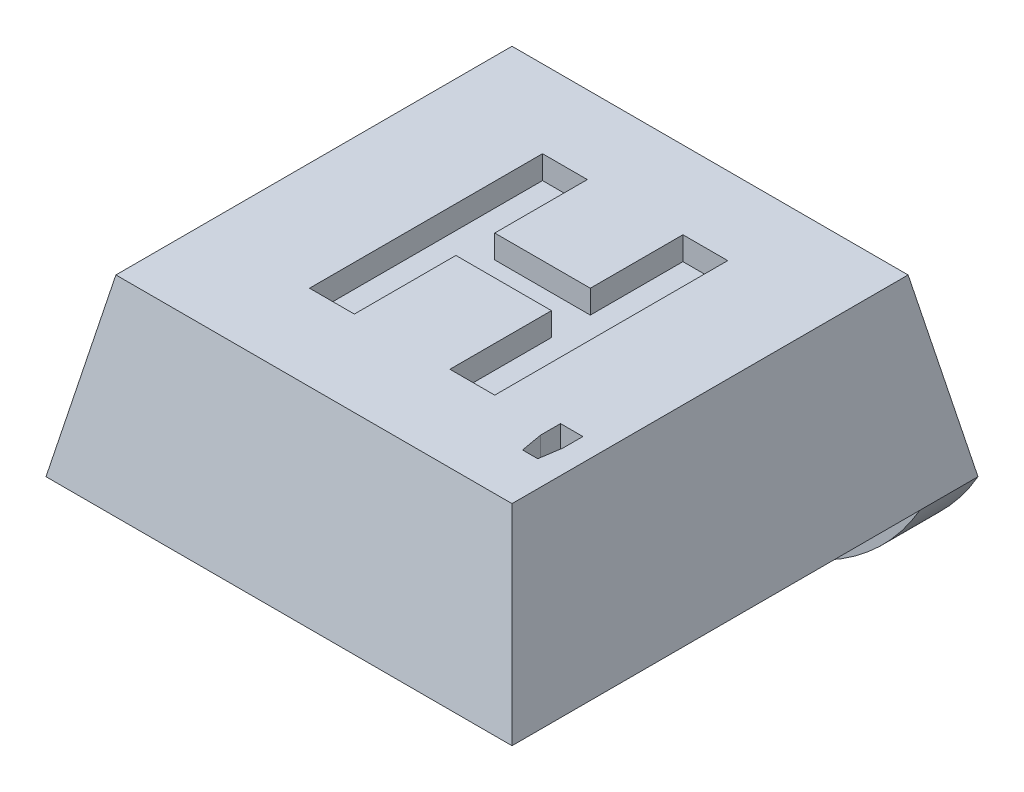
SolidWorks part; units mm, degrees
ref_plane "Front Plane" through (0, 0, 0) normal (0, 0, 1) x (1, 0, 0)
ref_plane "Top Plane" through (0, 0, 0) normal (0, 1, 0) x (1, 0, 0)
ref_plane "Right Plane" through (0, 0, 0) normal (1, 0, 0) x (0, 0, -1)
sketch "Sketch1" plane through (0, 0, 0) normal (0, 1, 0) x (1, 0, 0)
  line L1 (0, 0) -> (8, 0)
  line L2 (0, 0) -> (0, 8)
  line L3 (0, 8) -> (8, 8)
  line L4 (8, 0) -> (8, 8)
  dimension "D1" = 8
  dimension "D2" = 8
extrude "Boss-Extrude1" add sketch "Sketch1" along normal blind 3
sketch "Sketch2" plane through (0, 0, 0) normal (0, 0, 1) x (1, 0, 0)
  line L0 (0, 0) -> (0.6, 3)
  line L1 (0, 3) -> (8, 3) construction
  line L2 (0.6, 3) -> (0, 3)
  line L3 (0, 3) -> (0, 0)
  line L4 (8, 0) -> (7.4, 3)
  line L5 (7.4, 3) -> (8, 3)
  line L6 (8, 3) -> (8, 0)
  dimension "D1" = 0.6
  dimension "D2" = 0.6
extrude "Cut-Extrude1" cut sketch "Sketch2" against normal through all both and the other way through all
sketch "Sketch3" plane through (0, 0, 0) normal (1, 0, 0) x (0, 0, -1)
  line L0 (0, 0) -> (0.6, 3)
  line L1 (8, 3) -> (0, 3) construction
  line L2 (0.6, 3) -> (0, 3)
  line L3 (0, 3) -> (0, 0)
  line L4 (8, 3) -> (7.4, 3)
  line L5 (7.4, 3) -> (8, 0)
  line L6 (8, 3) -> (8, 0)
  dimension "D1" = 0.6
  dimension "D2" = 0.6
extrude "Cut-Extrude2" cut sketch "Sketch3" along normal blind 11
sketch "Sketch4" plane through (0, 0, 0) normal (0, -1, 0) x (1, 0, 0)
  line L0 (8, 0) -> (8, -8) construction
  line L3 (0, 0) -> (8, 0) construction
  circle A0 centre (4, -3.75) radius 1.8
  dimension "D1" = 3.6
  dimension "D2" = 4
  dimension "D3" = 3.75
extrude "Cut-Extrude3" cut sketch "Sketch4" against normal blind 0.8
sketch "Sketch5" plane through (0, 0, 0) normal (0, -1, 0) x (1, 0, 0)
  line L0 (8, 0) -> (8, -8) construction
  line L1 (0, -8) -> (8, -8)
  line L2 (0, -8) -> (0, -7)
  line L3 (0, -7) -> (8, -7)
  line L4 (8, -8) -> (8, -7)
  dimension "D1" = 1
extrude "Boss-Extrude2" add sketch "Sketch5" along normal blind 2
fillet "Fillet1" radius 4 2 edges at (8, -2, -7.5) (0, -2, -7.5)
sketch "Sketch6" plane through (0, 3, 0) normal (0, 1, 0) x (1, 0, 0)
  text T0 "H" font "Arial" height 4
extrude "Cut-Extrude4" cut sketch "Sketch6" against normal blind 0.4
sketch "Sketch7" plane through (0, 3, 0) normal (0, 1, 0) x (1, 0, 0)
  text T0 "'" font "Arial" height 2
extrude "Cut-Extrude5" cut sketch "Sketch7" against normal blind 0.4
